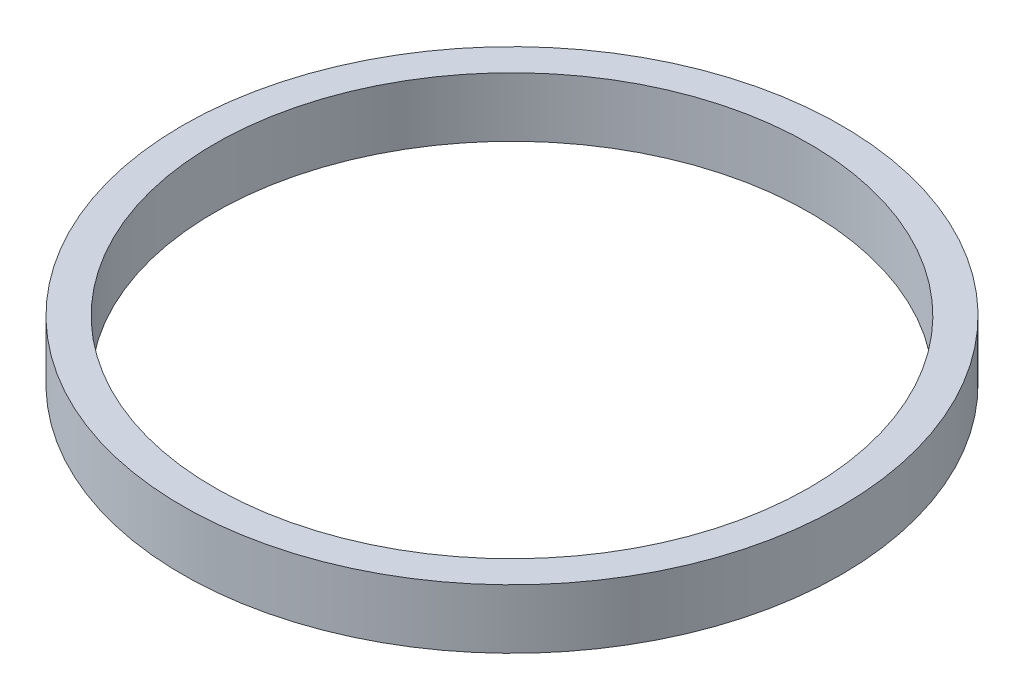
SolidWorks part; units mm, degrees
material "PET"
ref_plane "Front Plane" through (0, 0, 0) normal (0, 0, 1) x (1, 0, 0)
ref_plane "Top Plane" through (0, 0, 0) normal (0, 1, 0) x (1, 0, 0)
ref_plane "Right Plane" through (0, 0, 0) normal (1, 0, 0) x (0, 0, -1)
sketch "Sketch2" plane through (0, 0, 0) normal (0, 0, 1) x (1, 0, 0)
  line L0 (-65.2, 9.8) -> (-72.2, 9.8)
  line L2 (-72.2, 9.8) -> (-72.2, -3.2)
  line L3 (-72.2, -3.2) -> (-65.2, -3.2)
  line L4 (-65.2, -3.2) -> (-65.2, 9.8)
  line L6 (0, 0) -> (0, 30.013) construction
sketch "Sketch3" plane through (0, 0, 0) normal (0, 0, 1) x (1, 0, 0)
  line L4 (-65.2, 9.8) -> (-72.2, 9.8)
  line L5 (-72.2, 9.8) -> (-72.2, -3.2)
  line L6 (-72.2, -3.2) -> (-65.2, -3.2)
  line L7 (-65.2, -3.2) -> (-65.2, 9.8)
  line L8 (-65.2, 9.8) -> (-72.2, 9.8)
  line L9 (-72.2, 9.8) -> (-72.2, -3.2)
  line L10 (-72.2, -3.2) -> (-65.2, -3.2)
  line L11 (-65.2, -3.2) -> (-65.2, 9.8)
  dimension "D1" = 0
revolve "Revolve1" add sketch "Sketch3" angle 360 about L6
